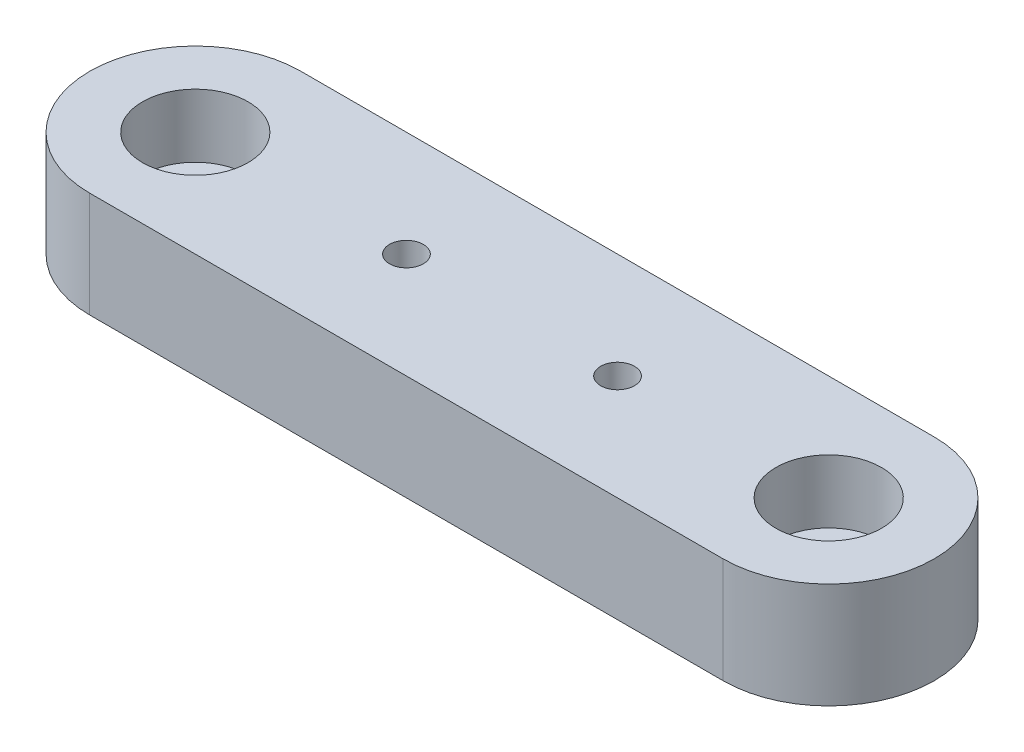
SolidWorks part; units mm, degrees
ref_plane "Front Plane" through (0, 0, 0) normal (0, 0, 1) x (1, 0, 0)
ref_plane "Top Plane" through (0, 0, 0) normal (0, 1, 0) x (1, 0, 0)
ref_plane "Right Plane" through (0, 0, 0) normal (1, 0, 0) x (0, 0, -1)
sketch "Sketch1" plane through (0, 0, 0) normal (0, 1, 0) x (1, 0, 0)
  line L0 (0, 10) -> (0, -10) construction
  line L1 (-40, 10) -> (40, 10)
  line L2 (-40, 10) -> (-40, -10)
  line L3 (-40, -10) -> (40, -10)
  line L4 (40, 10) -> (40, -10)
  line L5 (-40, 10) -> (40, -10) construction
  line L6 (-40, -10) -> (40, 10) construction
  line L7 (-40, 0) -> (40, 0) construction
  circle A0 centre (-10, 0) radius 1.6
  circle A2 centre (-30, 0) radius 3
  circle A3 centre (10, 0) radius 1.6
  circle A4 centre (30, 0) radius 3
  circle A5 centre (-30, 0) radius 10
  circle A6 centre (30, 0) radius 10
  point P0 (0, 0)
  dimension "D3" = 3.2
  dimension "D5" = 6
  dimension "D1" = 20
  dimension "D2" = 80
  dimension "D4" = 20
extrude "Boss-Extrude1" add sketch "Sketch1" along normal blind 10 contours A5 A2 | L3 A6 L1 A5 A0 A3 | A6 A4 region at (0, 0, 0) region at (-23.1289, 0, -6.8711) region at (36.8711, 0, -6.8711)
sketch "Sketch2" plane through (0, 10, 0) normal (0, 1, 0) x (1, 0, 0)
  line L0 (0, 10) -> (0, -10) construction
  line L3 (-30, -10) -> (30, -10) construction
  line L4 (-30, 10) -> (30, 10) construction
  circle A0 centre (-30, 0) radius 5
  circle A1 centre (30, 0) radius 5
  point P5 (0, 0)
  point P8 (0, 0)
  dimension "D1" = 10
extrude "Cut-Extrude1" cut sketch "Sketch2" against normal blind 6
hole_wizard "CSK for M3 Flat Head Machine Screw1" positions "Sketch3" profile "Sketch4" countersink size "M3" standard "ANSI Metric" end condition up to next
sketch "Sketch3" plane through (0, 0, 0) normal (0, -1, 0) x (-1, 0, 0)
  point P0 (10, 0)
  point P3 (-10, 0)
sketch "Sketch4" plane through (-10, 0, 0) normal (1, 0, 0) x (0, 0, -1)
  line L0 (0, 0) -> (0, 10)
  line L1 (0, 10) -> (1.5, 10)
  line L2 (1.5, 10) -> (1.5, 1.8)
  line L3 (1.5, 1.8) -> (3, 0.3)
  line L4 (3, 0.3) -> (3, 0)
  line L6 (3, 0) -> (0, 0)
  line L7 (-1.5, 1.8) -> (-3, 0.3) construction
  line L11 (0, -6.35) -> (0, 107.95) construction
  dimension "Thru Hole Dia." = 3
  dimension "Thru Hole Depth" = 10
  dimension "C'Sink Dia." = 6
  dimension "C'Sink Angle" = 90
  dimension "Head Clearance" = 0.3
